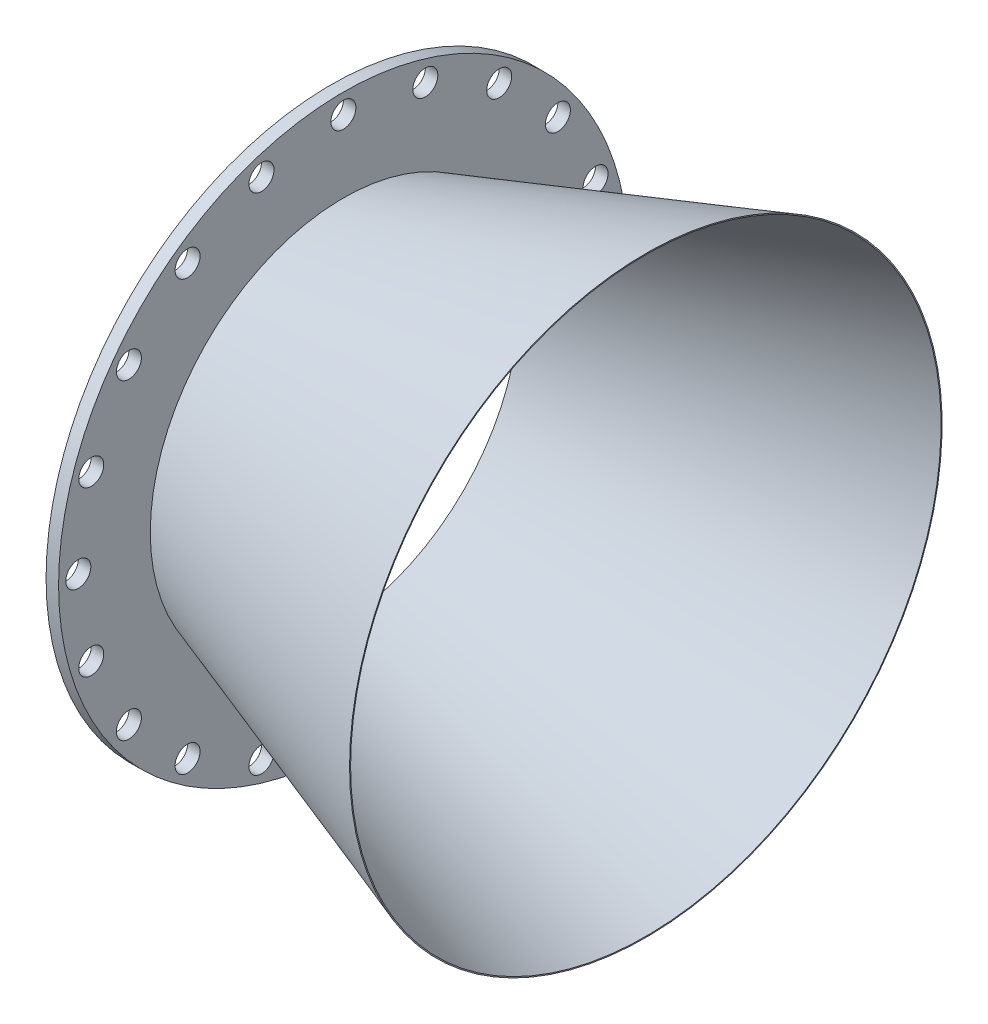
SolidWorks part; units mm, degrees
ref_plane "Front Plane" through (0, 0, 0) normal (0, 0, 1) x (1, 0, 0)
ref_plane "Top Plane" through (0, 0, 0) normal (0, 1, 0) x (1, 0, 0)
ref_plane "Right Plane" through (0, 0, 0) normal (1, 0, 0) x (0, 0, -1)
sketch "Sketch1" plane through (0, 0, 0) normal (0, 0, 1) x (1, 0, 0)
  line L0 (0, 0) -> (0, 47.6758) construction
  line L1 (0, 0) -> (79.9592, 0) construction
  line L2 (79.9592, 0) -> (79.9592, 74.9554) construction
  line L3 (0, 47.6758) -> (45.8899, 47.6758) construction
  line L4 (0, 47.6758) -> (62.4191, 65.9935) construction
  line L5 (79.9592, 74.9554) -> (173.3924, 74.9554) construction
  line L6 (79.9592, 74.9554) -> (185.7919, 93.6166) construction
  line L10 (0, 47.6758) -> (79.9592, 74.9554)
  line L11 (0, 47.9442) -> (79.9592, 75.2238)
  line L12 (79.9592, 74.9554) -> (79.9592, 75.2238)
  line L13 (0, 47.6758) -> (0, 47.9442)
  line L14 (-0.082, 47.9162) -> (79.8772, 75.1958) construction
  point P11 (79.9592, 75.224)
  dimension "D1" = 79.9592
  dimension "D2" = 47.6758
  dimension "D3" = 74.9554
  dimension "D4" = 16.355
  dimension "D5" = 10
  dimension "D6" = 0.254
revolve "Revolve1" add sketch "Sketch1" angle 360 about L1
sketch "Sketch3" plane through (0, 0, 0) normal (0, 0, 1) x (1, 0, 0)
  line L0 (79.9592, 75.2238) -> (0, 47.9442) construction
  line L1 (0, 47.9442) -> (3.175, 49.0274)
  line L2 (3.175, 49.0274) -> (3.175, 72.3138)
  line L3 (3.175, 72.3138) -> (0, 72.3138)
  line L4 (0, 72.3138) -> (0, 47.9442)
  line L5 (0, 0) -> (50000, 0) construction
  line L6 (0, 47.9442) -> (0, -47.9442) construction
  point P12 (0, 0)
  dimension "D1" = 3.175
  dimension "D2" = 72.3138
revolve "Revolve2" add sketch "Sketch3" angle 360 about L5
sketch "Sketch4" plane through (0, 0, 0) normal (-1, 0, 0) x (0, 0, 1)
  circle A0 centre (0, 67.31) radius 3.175
  circle A1 centre (20.7999, 64.0156) radius 3.175
  circle A2 centre (39.5638, 54.4549) radius 3.175
  circle A3 centre (54.4549, 39.5638) radius 3.175
  circle A4 centre (64.0156, 20.7999) radius 3.175
  circle A5 centre (67.31, 0) radius 3.175
  circle A6 centre (64.0156, -20.7999) radius 3.175
  circle A7 centre (54.4549, -39.5638) radius 3.175
  circle A8 centre (39.5638, -54.4549) radius 3.175
  circle A9 centre (20.7999, -64.0156) radius 3.175
  circle A10 centre (0, -67.31) radius 3.175
  circle A11 centre (-20.7999, -64.0156) radius 3.175
  circle A12 centre (-39.5638, -54.4549) radius 3.175
  circle A13 centre (-54.4549, -39.5638) radius 3.175
  circle A14 centre (-64.0156, -20.7999) radius 3.175
  circle A15 centre (-67.31, 0) radius 3.175
  circle A16 centre (-64.0156, 20.7999) radius 3.175
  circle A17 centre (-54.4549, 39.5638) radius 3.175
  circle A18 centre (-39.5638, 54.4549) radius 3.175
  circle A19 centre (-20.7999, 64.0156) radius 3.175
  point P44 (0, 0)
  dimension "D2" = 6.35
  dimension "D1" = 67.31
  dimension "D3" = 20
extrude "Cut-Extrude1" cut sketch "Sketch4" against normal up to next
